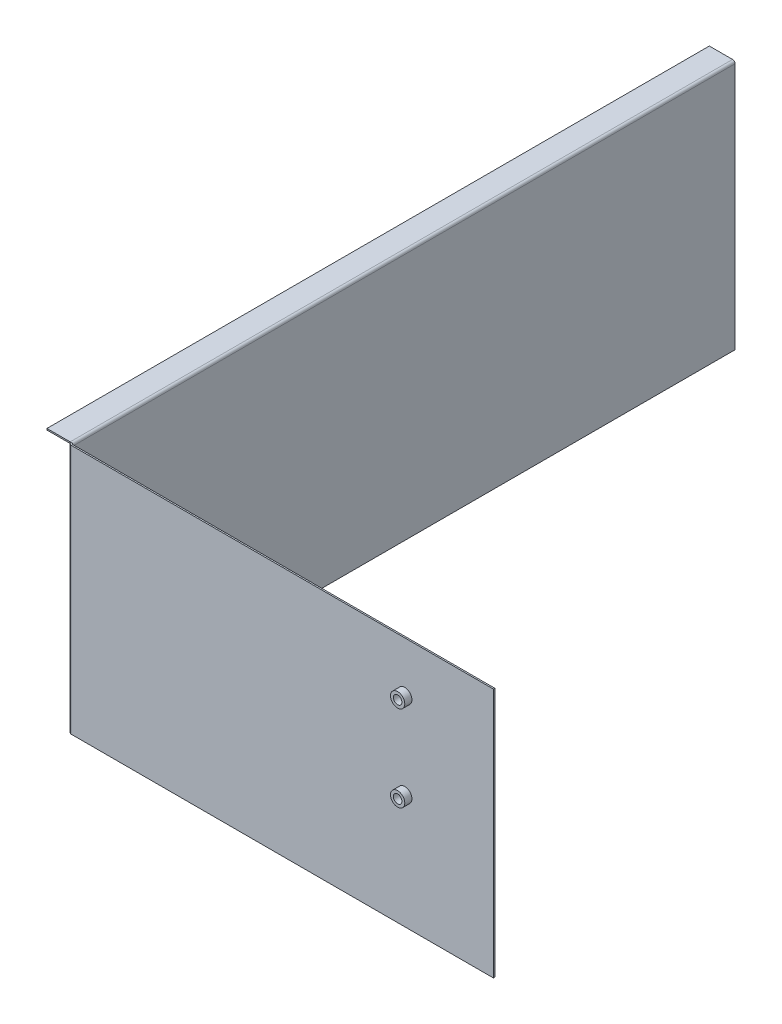
SolidWorks part; units mm, degrees
note: The reader was unsure of these and kept them because the rebuilt part matched: flange length of "Edge-Flange1", "Edge-Flange2".
ref_plane "Front Plane" through (0, 0, 0) normal (0, 0, 1) x (1, 0, 0)
ref_plane "Top Plane" through (0, 0, 0) normal (0, 1, 0) x (1, 0, 0)
ref_plane "Right Plane" through (0, 0, 0) normal (1, 0, 0) x (0, 0, -1)
sketch "Sketch1" plane through (0, 0, 0) normal (0, 0, 1) x (1, 0, 0)
  line L1 (-148.5, -87.5) -> (148.5, -87.5)
  line L2 (-148.5, -87.5) -> (-148.5, 87.5)
  line L3 (-148.5, 87.5) -> (148.5, 87.5)
  line L4 (148.5, -87.5) -> (148.5, 87.5)
  line L5 (-148.5, -87.5) -> (148.5, 87.5) construction
  line L6 (-148.5, 87.5) -> (148.5, -87.5) construction
  point P0 (0, 0)
  dimension "D1" = 297
  dimension "D2" = 175
base flange "Base-Flange1" sketch "Sketch1" thickness 1 reverse thickness direction no parameters "D1"=0.7366
sketch "Sketch6" [suppressed] plane through (0, 0, 0) normal (0, 0, 1) x (1, 0, 0)
  line L1 (-146, 110) -> (-646, 110)
  line L2 (-146, 110) -> (-146, -110)
  line L3 (-146, -110) -> (-646, -110)
  line L4 (-646, 110) -> (-646, -110)
  dimension "D1" = 500
sketch "Sketch9" [suppressed] plane through (0, 0, -1) normal (0, 0, -1) x (-1, 0, 0)
  line L0 (146, 110) -> (146, -110)
  line L1 (146, -110) -> (-146, -110) construction
  line L2 (146, -110) -> (146, 110) construction
edge flange "Edge-Flange1" sketch "Sketch12" flange angle 90 flange length 465 flange position material inside bend radius 0.7366 thickness 1 relief rectangular parameters "D6"=10
sketch "Sketch12" plane through (-148.5, 0, -1) normal (1, 0, 0) x (0, -1, 0)
  line L2 (-87.5, 0) -> (-87.5, 464)
  line L3 (-87.5, 464) -> (87.5, 464)
  line L4 (87.5, 464) -> (87.5, 0)
  line L5 (87.5, 0) -> (-87.5, 0) construction
  line L6 (87.5, 0) -> (-87.5, 0)
bend "EdgeBend1" bend radius 0.7366 bend angle 90 parameters "D5"=1
edge flange "Edge-Flange2" sketch "Sketch15" flange angle 90 flange length 18 flange position material inside bend radius 0.7366 thickness 1 relief none parameters "D6"=10
sketch "Sketch15" plane through (-148.5, 87.5, 0) normal (0, 1, 0) x (0, 0, -1)
  line L0 (465, 0) -> (1.7366, 0) construction
  line L1 (465, 0) -> (1.7366, 0)
  line L2 (1.7366, 0) -> (1.7366, 17)
  line L3 (1.7366, 17) -> (465, 17)
  line L4 (465, 17) -> (465, 0)
bend "EdgeBend2" bend radius 0.7366 bend angle 90 parameters "D5"=2
sketch "Sketch17" plane through (-148.5, 0, 0) normal (-1, 0, 0) x (0, 0, 1)
  circle A0 centre (-402.6069, 78.4539) radius 2.794
  circle A1 centre (-292.5995, 78.4539) radius 2.794
  circle A2 centre (-182.5921, 78.4539) radius 2.794
  circle A3 centre (-72.5847, 78.4539) radius 2.794
  circle A4 centre (-72.5847, 78.4539) radius 4.794
  circle A5 centre (-182.5921, 78.4539) radius 4.794
  circle A6 centre (-292.5995, 78.4539) radius 4.794
  circle A7 centre (-402.6069, 78.4539) radius 4.794
  dimension "D1" = 2
extrude "Boss-Extrude1" add sketch "Sketch17" along normal blind 18
sketch "Sketch21" plane through (0, 0, 0) normal (0, 0, 1) x (1, 0, 0)
  line L0 (148.5, -87.5) -> (148.5, 87.5) construction
  line L1 (148.5, 87.5) -> (-146.7634, 87.5) construction
  circle A0 centre (86.5, 52.5) radius 3
  circle A2 centre (86.5, 52.5) radius 5
  circle A3 centre (86.5, -7.5) radius 3
  circle A4 centre (86.5, -7.5) radius 5
  point P10 (0, 0)
  dimension "D1" = 6
  dimension "D2" = 10
  dimension "D3" = 60
  dimension "D4" = 62
  dimension "D5" = 35
extrude "Boss-Extrude2" add sketch "Sketch21" along normal blind 5
sketch "Bend-Lines1" [suppressed] plane through (0, 0, 0) normal (0, 1, 0) x (1, 0, 0)
sketch "Bounding-Box1" [suppressed] plane through (0, 0, 0) normal (0, 1, 0) x (1, 0, 0)
sheet metal parameters "Sheet-Metal1" thickness 1 parameters "D1"=0.7366
flat pattern "Flat-Pattern1" [suppressed]
sketch "Bend-Lines2" plane through (0, 0, 0) normal (0, 1, 0) x (1, 0, 0)
sketch3d "Bounding-Box2" [suppressed]
  line L0 (-146, -110, 0) -> (146, -110, 0) construction
  line L1 (-146, 110, 0) -> (146, 110, 0) construction
  line L2 (-146, -110, 0) -> (-146, 110, 0) construction
  line L3 (146, -110, 0) -> (146, 110, 0) construction
sheet metal parameters "Sheet-Metal3" thickness 1 parameters "D1"=0.7366
flat pattern "Flat-Pattern1"
sketch "Bend-Lines2" plane through (0, 0, 0) normal (0, 0, 1) x (1, 0, 0)
  line L0 (-145.2346, 87.5) -> (-145.2346, -87.5) construction
  line L1 (-145.2346, 87.5) -> (-145.2346, -87.5) construction
sketch3d "Bounding-Box2" [suppressed]
  line L0 (-603.4692, -87.5, 0) -> (146, -87.5, 0) construction
  line L1 (-603.4692, 87.5, 0) -> (146, 87.5, 0) construction
  line L2 (-603.4692, -87.5, 0) -> (-603.4692, 87.5, 0) construction
  line L3 (146, -87.5, 0) -> (146, 87.5, 0) construction
bend of the flat pattern "Flatten-<EdgeBend1>1"
sheet metal parameters "Sheet-Metal4" thickness 1 parameters "D1"=0.7366
flat pattern "Flat-Pattern1"
sketch "Bend-Lines2" plane through (0, 0, 0) normal (0, 0, 1) x (1, 0, 0)
  line L0 (-142.7346, 87.5) -> (-142.7346, -87.5) construction
  line L1 (-142.7346, 87.5) -> (-142.7346, -87.5) construction
  line L2 (-143.7058, 86.7346) -> (-606.9692, 86.7346) construction
  line L3 (-143.7058, 86.7346) -> (-606.9692, 86.7346) construction
sketch3d "Bounding-Box2" [suppressed]
  line L0 (-606.9692, -87.5, 0) -> (143.5, -87.5, 0) construction
  line L1 (-606.9692, 103.9692, 0) -> (143.5, 103.9692, 0) construction
  line L2 (-606.9692, -87.5, 0) -> (-606.9692, 103.9692, 0) construction
  line L3 (143.5, -87.5, 0) -> (143.5, 103.9692, 0) construction
bend of the flat pattern "Flatten-<EdgeBend1>1"
bend of the flat pattern "Flatten-<EdgeBend2>1"
sheet metal parameters "Sheet-Metal5" thickness 1 parameters "D1"=0.7366
flat pattern "Flat-Pattern1"
sketch "Bend-Lines2" plane through (0, 0, 0) normal (0, 0, 1) x (1, 0, 0)
  line L0 (-142.7346, 87.5) -> (-142.7346, -87.5) construction
  line L1 (-142.7346, 87.5) -> (-142.7346, -87.5) construction
  line L2 (-143.7058, 86.7346) -> (-606.9692, 86.7346) construction
  line L3 (-143.7058, 86.7346) -> (-606.9692, 86.7346) construction
sketch3d "Bounding-Box2" [suppressed]
  line L0 (-606.9692, -87.5, 0) -> (143.5, -87.5, 0) construction
  line L1 (-606.9692, 103.9692, 0) -> (143.5, 103.9692, 0) construction
  line L2 (-606.9692, -87.5, 0) -> (-606.9692, 103.9692, 0) construction
  line L3 (143.5, -87.5, 0) -> (143.5, 103.9692, 0) construction
bend of the flat pattern "Flatten-<EdgeBend1>1"
bend of the flat pattern "Flatten-<EdgeBend2>1"
sheet metal parameters "Sheet-Metal6" thickness 1 parameters "D1"=0.7366
flat pattern "Flat-Pattern1"
sketch "Bend-Lines2" plane through (0, 0, 0) normal (0, 0, 1) x (1, 0, 0)
  line L0 (-147.7346, 87.5) -> (-147.7346, -87.5) construction
  line L1 (-147.7346, 87.5) -> (-147.7346, -87.5) construction
  line L2 (-148.7058, 86.7346) -> (-611.9692, 86.7346) construction
  line L3 (-148.7058, 86.7346) -> (-611.9692, 86.7346) construction
sketch3d "Bounding-Box2" [suppressed]
  line L0 (-611.9692, -87.5, 0) -> (148.5, -87.5, 0) construction
  line L1 (-611.9692, 103.9692, 0) -> (148.5, 103.9692, 0) construction
  line L2 (-611.9692, -87.5, 0) -> (-611.9692, 103.9692, 0) construction
  line L3 (148.5, -87.5, 0) -> (148.5, 103.9692, 0) construction
bend of the flat pattern "Flatten-<EdgeBend1>1"
bend of the flat pattern "Flatten-<EdgeBend2>1"
